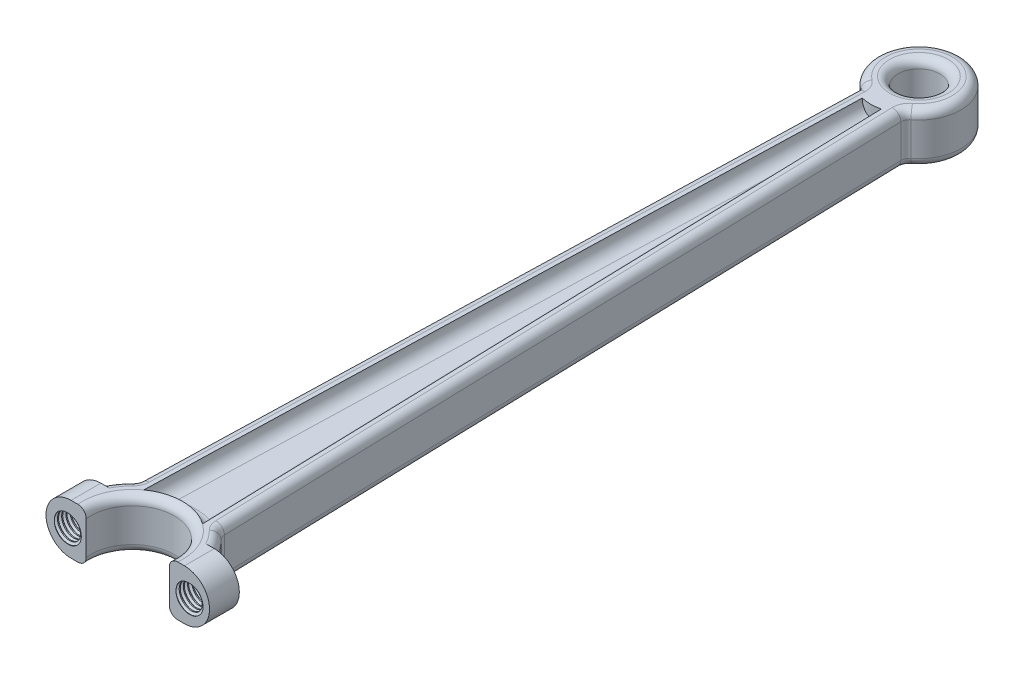
SolidWorks part; units mm, degrees
ref_plane "Front Plane" through (0, 0, 0) normal (0, 0, 1) x (1, 0, 0)
ref_plane "Top Plane" through (0, 0, 0) normal (0, 1, 0) x (1, 0, 0)
ref_plane "Right Plane" through (0, 0, 0) normal (1, 0, 0) x (0, 0, -1)
sketch "Sketch1" plane through (0, 0, 0) normal (0, 1, 0) x (1, 0, 0)
  line L0 (10, -188.1) -> (20, -188.1)
  line L1 (-15, -188.1) -> (-20, -188.1)
  line L2 (0, -188.1) -> (0, -178.1)
  line L3 (20, -188.1) -> (-20, -188.1)
  line L4 (-20, -182.1) -> (-20, -188.1)
  line L5 (0, -188.1) -> (0, -10)
  line L6 (20, -182.1) -> (20, -188.1)
  line L7 (-20, -188.1) -> (-10, -188.1)
  line L8 (-20, -182.1) -> (-8, -182.1)
  line L9 (-20, -188.1) -> (-15, -188.1)
  line L10 (-20, -188.1) -> (-20, -199.2288)
  line L11 (-20, -188.1) -> (20, -188.1)
  line L12 (20, -182.1) -> (8, -182.1)
  line L13 (-20, -199.2288) -> (-10.0573, -199.2288)
  line L14 (20, -188.1) -> (20, -199.2288)
  line L15 (10.0573, -199.2288) -> (20, -199.2288)
  line L16 (-5, 0) -> (-9.9946, -176.9148)
  line L17 (-25, -188.1) -> (25, -188.1)
  line L18 (-25, -188.1) -> (-25, -203.1)
  line L19 (-25, -203.1) -> (25, -203.1)
  line L20 (25, -188.1) -> (25, -203.1)
  line L21 (9.9946, -176.9148) -> (5, 0)
  arc A0 (-5.1991, -8.5422) -> (5.2425, -8.5156) centre (0, 0) ccw
  circle A1 centre (0, 0) radius 10
  arc A2 (-10.0573, -199.2288) -> (10.0573, -199.2288) centre (0, -188.1) ccw
  arc A3 (-9.9946, -176.9148) -> (-13.7477, -182.1) centre (0, -188.1) ccw
  circle A4 centre (0, -188.1) radius 10
  arc A5 (13.7477, -182.1) -> (9.9946, -176.9148) centre (0, -188.1) ccw
  circle A6 centre (0, 0) radius 5
  point P16 (0, -182.1)
  point P29 (-20, -185.1)
  dimension "D6" = 20
  dimension "D7" = 6
  dimension "D3" = 188.1
  dimension "D4" = 10
  dimension "D5" = 15
  dimension "D8" = 20
  dimension "D15" = 20
  dimension "D19" = 0
  dimension "D9" = 20
  dimension "D24" = 10
  dimension "D10" = 1.617
  dimension "D11" = 10.0054
  dimension "D12" = 10.0054
  dimension "D13" = 20
  dimension "D14" = 6
  dimension "D16" = 9.9427
  dimension "D17" = 5
  dimension "D18" = 40
  dimension "D20" = 15
  dimension "D21" = 25
  dimension "D22" = 25
  dimension "D23" = 12
extrude "Boss-Extrude1" add sketch "Sketch1" along normal blind 12 contours A4 L5 A0 A1 L16 A3 L8 | L12 A5 L21 A0 L5 A4 | A4 L8 L4 L1 L3 | A4 L0 L6 L12 | A4 L3 L1 L10 L13 A2 L15 L14 L0 | A6 L21 A0 A1 L16 | A6 L16 A1 A0 L21 region at (14.6651, 0, 185.0082) region at (15, 0, 188.5272) region at (4.0591, 0, 104.2402) region at (-14.6651, 0, 185.0082) region at (-4.0591, 0, 104.2402) region at (0, 0, 6.6171) region at (5.3927, 0, 4.2508)
sketch "Sketch2" plane through (0, 12, 0) normal (0, 1, 0) x (1, 0, 0)
  line L0 (7.035, -178.3785) -> (2.2783, -11.287)
  line L1 (-2.2783, -11.287) -> (-7.035, -178.3785)
  line L8 (9.9946, -176.9148) -> (5.2404, -8.5169)
  line L9 (9.9946, -176.9148) -> (5.2404, -8.5169)
  line L10 (-5.2404, -8.5169) -> (-9.9946, -176.9148)
  line L11 (-20, -182.1) -> (-20, -199.2288)
  line L12 (-20, -199.2288) -> (-10.0573, -199.2288)
  line L13 (10.0573, -199.2288) -> (20, -199.2288)
  line L14 (20, -199.2288) -> (20, -182.1)
  line L15 (-5.2404, -8.5169) -> (-9.9946, -176.9148)
  line L16 (-13.7477, -182.1) -> (-20, -182.1)
  line L17 (-13.7477, -182.1) -> (-20, -182.1)
  line L19 (-20, -182.1) -> (-20, -199.2288)
  line L20 (-20, -199.2288) -> (-10.0573, -199.2288)
  line L22 (20, -182.1) -> (13.7477, -182.1)
  line L23 (20, -182.1) -> (13.7477, -182.1)
  line L24 (7.035, -178.3785) -> (2.1903, -8.1985) construction
  line L25 (-2.1903, -8.1985) -> (-7.035, -178.3785) construction
  line L26 (-13.7477, -182.1) -> (-20, -182.1) construction
  line L27 (-17, -185.1) -> (-17, -196.2288) construction
  line L28 (-11.6189, -185.1) -> (-17, -185.1) construction
  line L29 (-17, -196.2288) -> (-8.8274, -196.2288) construction
  line L30 (8.8274, -196.2288) -> (17, -196.2288) construction
  line L31 (10.0573, -199.2288) -> (20, -199.2288) construction
  line L32 (17, -196.2288) -> (17, -185.1) construction
  line L33 (20, -199.2288) -> (20, -182.1) construction
  line L34 (17, -185.1) -> (11.6189, -185.1) construction
  line L35 (20, -182.1) -> (13.7477, -182.1) construction
  line L36 (9.9946, -176.9148) -> (5.2447, -10.0643) construction
  line L37 (-5.2447, -10.0643) -> (-9.9946, -176.9148) construction
  arc A0 (7.035, -178.3785) -> (-7.035, -178.3785) centre (0, -188.1) ccw
  arc A1 (5.2447, -10.0643) -> (-5.2447, -10.0643) centre (0, -1.55) ccw construction
  arc A4 (5.2404, -8.5169) -> (-5.2404, -8.5169) centre (0, 0) ccw
  arc A5 (-9.9946, -176.9148) -> (-13.7477, -182.1) centre (0, -188.1) ccw
  arc A6 (-10.0573, -199.2288) -> (10.0573, -199.2288) centre (0, -188.1) ccw
  arc A7 (13.7477, -182.1) -> (9.9946, -176.9148) centre (0, -188.1) ccw
  arc A10 (5.2404, -8.5169) -> (-5.2404, -8.5169) centre (0, 0) ccw
  arc A12 (-2.2783, -11.287) -> (2.2783, -11.287) centre (0, -1.55) ccw
  arc A13 (2.1903, -8.1985) -> (-2.1903, -8.1985) centre (0, -1.55) ccw construction
  arc A14 (-9.9946, -176.9148) -> (-13.7477, -182.1) centre (0, -188.1) ccw construction
  arc A15 (-7.035, -178.3785) -> (-11.6189, -185.1) centre (0, -188.1) ccw construction
  arc A16 (-8.8274, -196.2288) -> (8.8274, -196.2288) centre (0, -188.1) ccw construction
  arc A17 (-10.0573, -199.2288) -> (10.0573, -199.2288) centre (0, -188.1) ccw construction
  arc A18 (13.7477, -182.1) -> (9.9946, -176.9148) centre (0, -188.1) ccw construction
  arc A19 (11.6189, -185.1) -> (7.035, -178.3785) centre (0, -188.1) ccw construction
  dimension "D3" = 10
  dimension "D1" = 0
  dimension "D2" = 3
extrude "Cut-Extrude1" cut sketch "Sketch2" against normal blind 3 contours A12 L1 A0 L0 region at (0, 12, 108.1345)
fillet "Fillet1" radius 3 3 edges at (4.6566, 9, 94.8327) (0, 9, 176.1) (-4.6566, 9, 94.8327)
sketch "Sketch3" plane through (0, 0, 0) normal (0, -1, 0) x (1, 0, 0)
  line L0 (2.1939, 6.6473) -> (7.0346, 178.3782)
  line L1 (11.6189, 185.1) -> (17, 185.1)
  line L2 (17, 185.1) -> (17, 196.2288)
  line L3 (17, 196.2288) -> (8.8274, 196.2288)
  line L4 (-8.8274, 196.2288) -> (-17, 196.2288)
  line L5 (-17, 196.2288) -> (-17, 185.1)
  line L6 (-17, 185.1) -> (-11.6189, 185.1)
  line L7 (-7.0379, 178.3805) -> (-1.8075, 6.7626)
  line L8 (-9.9946, 176.9148) -> (-5.2404, 8.5169)
  line L9 (-9.9946, 176.9148) -> (-5.2404, 8.5169)
  line L10 (20, 182.1) -> (20, 199.2288)
  line L11 (20, 199.2288) -> (10.0573, 199.2288)
  line L12 (-10.0573, 199.2288) -> (-20, 199.2288)
  line L13 (-20, 199.2288) -> (-20, 182.1)
  line L14 (13.7477, 182.1) -> (20, 182.1)
  line L15 (13.7477, 182.1) -> (20, 182.1)
  line L16 (-20, 182.1) -> (-13.7477, 182.1)
  line L17 (-20, 182.1) -> (-13.7477, 182.1)
  line L18 (20, 182.1) -> (20, 199.2288)
  line L19 (20, 199.2288) -> (10.0573, 199.2288)
  line L20 (-10.0573, 199.2288) -> (-20, 199.2288)
  line L21 (-20, 199.2288) -> (-20, 182.1)
  line L22 (5.2404, 8.5169) -> (9.9946, 176.9148)
  line L23 (5.2404, 8.5169) -> (9.9946, 176.9148)
  line L32 (5.2477, 8.5125) -> (9.9946, 176.9148) construction
  line L33 (13.7477, 182.1) -> (20, 182.1) construction
  line L34 (-20, 182.1) -> (-13.7477, 182.1) construction
  line L35 (-9.9946, 176.9148) -> (-4.869, 8.7346) construction
  arc A0 (7.0346, 178.3782) -> (11.6189, 185.1) centre (0, 188.1) ccw
  arc A1 (8.8274, 196.2288) -> (-8.8274, 196.2288) centre (0, 188.1) ccw
  arc A2 (-11.6189, 185.1) -> (-7.0379, 178.3805) centre (0, 188.1) ccw
  arc A3 (-1.8075, 6.7626) -> (2.1939, 6.6473) centre (0, 0) ccw
  arc A4 (9.9946, 176.9148) -> (13.7477, 182.1) centre (0, 188.1) ccw
  arc A5 (10.0573, 199.2288) -> (-10.0573, 199.2288) centre (0, 188.1) ccw
  arc A6 (-13.7477, 182.1) -> (-9.9946, 176.9148) centre (0, 188.1) ccw
  arc A7 (-5.2404, 8.5169) -> (5.2404, 8.5169) centre (0, 0) ccw
  arc A8 (9.9946, 176.9148) -> (13.7477, 182.1) centre (0, 188.1) ccw
  arc A9 (10.0573, 199.2288) -> (-10.0573, 199.2288) centre (0, 188.1) ccw
  arc A10 (-13.7477, 182.1) -> (-9.9946, 176.9148) centre (0, 188.1) ccw
  arc A11 (-5.2404, 8.5169) -> (5.2404, 8.5169) centre (0, 0) ccw
  circle A12 centre (0, 0) radius 7
  circle A13 centre (0, 188.1) radius 12
  arc A18 (-4.869, 8.7346) -> (5.2477, 8.5125) centre (0, 0) ccw construction
  dimension "D1" = 0
  dimension "D2" = 3
extrude "Cut-Extrude2" cut sketch "Sketch3" against normal blind 3 contours A13 L7 A12 L0 region at (0.0796, 0, 107.5532)
fillet "Fillet2" radius 3 3 edges at (4.6143, 3, 92.5127) (-4.4227, 3, 92.5716) (-0.002, 3, 176.1)
fillet "Fillet3" radius 2 18 edges at (-12.151, 12, 179.3049) (-12.151, 0, 179.3049) (12.151, 12, 179.3049) (12.151, 0, 179.3049) (0, 0, 198.1) (0, 12, 198.1) (0, 12, -10) (0, 0, -10) (0, 0, 5) (0, 12, 5) (9.9946, 6, 176.9148) (7.6175, 12, 92.7159) (5.2404, 6, 8.5169) (7.6175, 0, 92.7159) (-5.2404, 6, 8.5169) (-7.6175, 12, 92.7159) (-9.9946, 6, 176.9148) (-7.6175, 0, 92.7159)
sketch "Sketch4" plane through (0, 0, 199.2288) normal (0, 0, 1) x (1, 0, 0)
  line L0 (10.0573, 12) -> (20, 12) construction
  line L1 (10.0573, 12) -> (10.0573, 0) construction
  line L2 (0, 0) -> (0, 10.0701)
  line L3 (10.0573, 12) -> (13.5573, 12)
  line L4 (10.0573, 12) -> (10.0573, 0)
  line L5 (10.0573, 0) -> (13.5573, 0)
  line L6 (13.5573, 12) -> (13.5573, 0)
  line L7 (13.5573, 12) -> (19.5573, 12)
  line L8 (13.5573, 12) -> (13.5573, 0)
  line L9 (13.5573, 0) -> (19.5573, 0)
  line L11 (-20, 12) -> (-13.5573, 12)
  line L12 (-13.5573, 0) -> (-19.5573, 0)
  line L13 (-13.5573, 12) -> (-13.5573, 0)
  line L14 (-13.5573, 12) -> (-19.5573, 12)
  line L15 (-13.5573, 12) -> (-13.5573, 0)
  line L16 (-10.0573, 0) -> (-13.5573, 0)
  line L17 (-10.0573, 12) -> (-10.0573, 0)
  line L18 (-10.0573, 12) -> (-13.5573, 12)
  line L19 (-20, 12) -> (-20, 0)
  line L20 (13.5573, 12) -> (20, 12)
  line L21 (13.5573, 12) -> (13.5573, 0)
  line L22 (13.5573, 0) -> (20, 0)
  line L23 (20, 12) -> (20, 0)
  line L24 (-20, 0) -> (-13.5573, 0)
  line L25 (-13.5573, 12) -> (-13.5573, 0)
  circle A0 centre (13.5573, 6) radius 6
  circle A1 centre (-13.5573, 6) radius 6
  line M1 (10.0573, 0) -> (20, 0)
  line M2 (20, 0) -> (20, 12)
  line M3 (20, 12) -> (10.0573, 12)
  dimension "D1" = 6
  dimension "D2" = 12
  dimension "D3" = 3.5
  dimension "D4" = 6.4427
extrude "Cut-Extrude3" cut sketch "Sketch4" against normal through all contours L12 A1 L11 L19 L24 | A0 M1 M2 M3 region at (16.5573, 11.8638, 199.2288) region at (-19.7787, 11.8638, 199.2288)
sketch "Sketch5" plane through (0, 0, 199.2288) normal (0, 0, 1) x (1, 0, 0)
  line L0 (-10.0573, 12) -> (-10.0573, 0) construction
  line L1 (10.0573, 12) -> (-10.0573, 12) construction
  line L2 (0, 12) -> (0, 0)
  circle A0 centre (-14.5573, 6) radius 3
  circle A1 centre (14.5573, 6) radius 3
  dimension "D1" = 6
  dimension "D2" = 4.5
  dimension "D3" = 6
extrude "Cut-Extrude4" cut sketch "Sketch5" against normal blind 15 contours A0 | A1 region at (-14.5573, 6, 199.2288) region at (14.5573, 6, 199.2288)
thread "Thread1" pitch 1 method cut profile "Thread Profile1" start angle 0, offset 1, length 15, pitch 1, diameter 6
ref_plane "Plane1" through (11.5573, 6, 200.2288) normal (0, -1, 0) x (-1, 0, 0)
sketch "Thread Profile1" plane through (11.5573, 6, 200.2288) normal (0, -1, 0) x (-1, 0, 0)
  line L0 (0, 0) -> (0, 1) construction
  line L1 (0, 0) -> (0.5413, 0.3125)
  line L2 (0.5413, 0.3125) -> (0.5413, 0.4375)
  line L3 (0.5413, 0.4375) -> (0, 0.75)
  line L4 (0.5413, 0.375) -> (0, 0.375) construction
  line L11 (0, 0) -> (0, 0.75)
  point P2 (0, 0)
  dimension "Pitch" = 1
  dimension "Profile_Angle" = 60
  dimension "Profile_Land" = 0.125
  dimension "Profile_Height" = 0.5413
thread "Thread2" pitch 1 method cut profile "Thread Profile2" start angle 0, offset 1, length 15, pitch 1, diameter 6
ref_plane "Plane2" through (-17.5573, 6, 200.2288) normal (0, -1, 0) x (-1, 0, 0)
sketch "Thread Profile2" plane through (-17.5573, 6, 200.2288) normal (0, -1, 0) x (-1, 0, 0)
  line L0 (0, 0) -> (0, 1) construction
  line L1 (0, 0) -> (0.5413, 0.3125)
  line L2 (0.5413, 0.3125) -> (0.5413, 0.4375)
  line L3 (0.5413, 0.4375) -> (0, 0.75)
  line L4 (0.5413, 0.375) -> (0, 0.375) construction
  line L11 (0, 0) -> (0, 0.75)
  point P2 (0, 0)
  dimension "Pitch" = 1
  dimension "Profile_Angle" = 60
  dimension "Profile_Land" = 0.125
  dimension "Profile_Height" = 0.5413
sketch "Sketch7" plane through (0, 0, 199.2288) normal (0, 0, 1) x (1, 0, 0)
  circle A0 centre (-14.5573, 6) radius 4
  circle A1 centre (14.5573, 6) radius 4
  dimension "D1" = 8
  dimension "D2" = 8
extrude "Cut-Extrude6" cut sketch "Sketch7" against normal blind 10
sketch "Sketch8" plane through (0, 0, 0) normal (0, -1, 0) x (1, 0, 0)
  line L0 (-13.5573, 199.2288) -> (-10.0573, 199.2288) construction
  line L1 (-19.9427, 204.2288) -> (20.0573, 204.2288)
  line L2 (-19.9427, 204.2288) -> (-19.9427, 189.2288)
  line L3 (-19.9427, 189.2288) -> (20.0573, 189.2288)
  line L4 (20.0573, 204.2288) -> (20.0573, 189.2288)
  line L5 (13.5573, 182.1) -> (13.5573, 199.2288) construction
  circle A0 centre (0, 188.1) radius 12 construction
  point P9 (0.0573, 198.5499)
  dimension "D1" = 5
  dimension "D2" = 15
  dimension "D3" = 20
  dimension "D4" = 20
  dimension "D5" = 6.5
extrude "Cut-Extrude8" cut sketch "Sketch8" against normal through all
